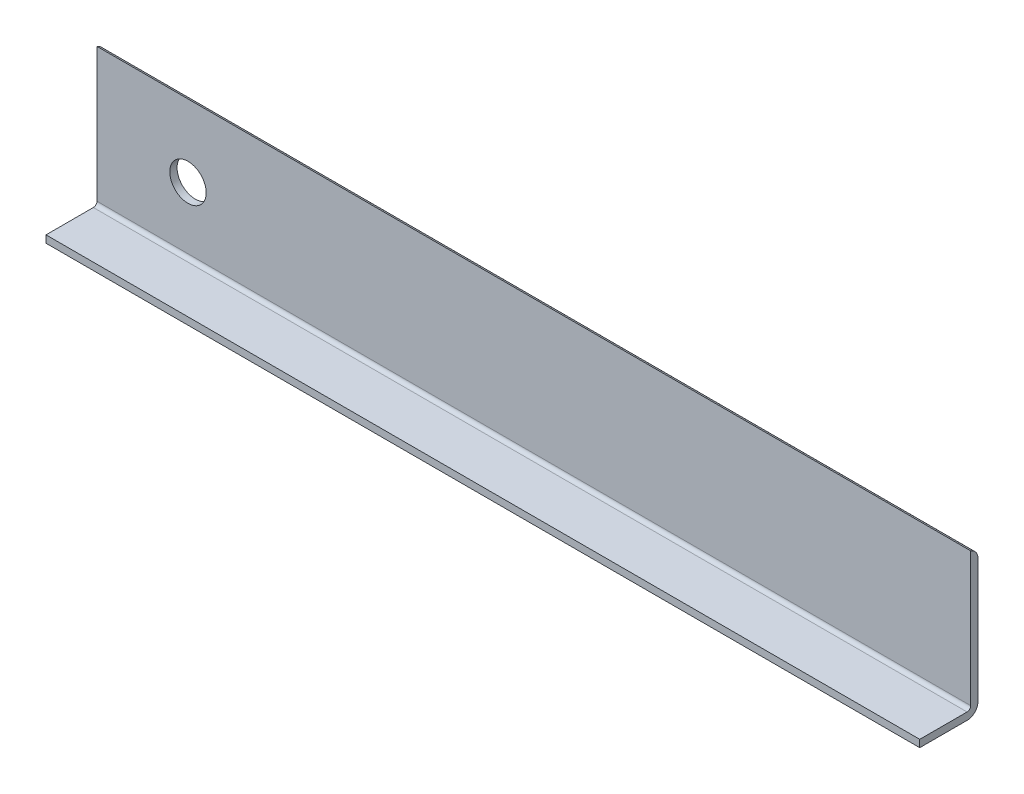
SolidWorks part; units mm, degrees
ref_plane "Спереди" through (0, 0, 0) normal (0, 0, 1) x (1, 0, 0)
ref_plane "Сверху" through (0, 0, 0) normal (0, 1, 0) x (1, 0, 0)
ref_plane "Справа" through (0, 0, 0) normal (1, 0, 0) x (0, 0, -1)
sketch "Эскиз1" plane through (0, 0, 0) normal (1, 0, 0) x (0, 0, -1)
  line L1 (1, 0) -> (15, 0)
  line L2 (0, 1) -> (0, 35)
  line L3 (1, 36) -> (15, 36)
  line L4 (16, 1) -> (16, 35)
  arc A4 (1, 0) -> (0, 1) centre (1, 1) cw
  arc A5 (15, 0) -> (16, 1) centre (15, 1) ccw
  arc A6 (16, 35) -> (15, 36) centre (15, 35) ccw
  arc A7 (0, 35) -> (1, 36) centre (1, 35) cw
  point P3 (0, 0)
  point P8 (0, 0)
  dimension "D1" = 1
extrude "Вытянуть-Тонкостенный1" add sketch "Эскиз1" along normal blind 240 thin thin type one direction wall 2
sketch "Эскиз2" plane through (0, -2, 0) normal (0, -1, 0) x (1, 0, 0)
  line L0 (240, -1) -> (240, -15) construction
  line L1 (0, 2) -> (240, 2)
  line L2 (0, 2) -> (0, -2)
  line L3 (0, -2) -> (240, -2)
  line L4 (240, 2) -> (240, -2)
extrude "Вырез-Вытянуть1" cut sketch "Эскиз2" against normal blind 25
sketch "Эскиз3" plane through (0, 38, 0) normal (0, 1, 0) x (1, 0, 0)
  line L1 (0, 16) -> (240, 16)
  line L2 (0, 16) -> (0, -2)
  line L3 (0, -2) -> (240, -2)
  line L4 (240, 16) -> (240, -2)
extrude "Вырез-Вытянуть2" cut sketch "Эскиз3" against normal blind 25
sketch "Эскиз4" plane through (0, 0, -18) normal (0, 0, -1) x (-1, 0, 0)
  circle A0 centre (-25, 18) radius 5
extrude "Вырез-Вытянуть3" cut sketch "Эскиз4" against normal blind 10
